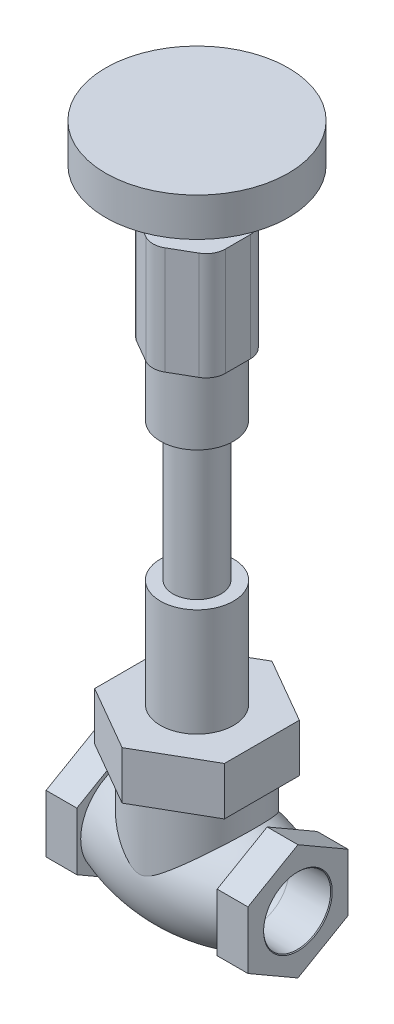
SolidWorks part; units mm, degrees
ref_plane "Front" through (0, 0, 0) normal (0, 0, 1) x (1, 0, 0)
ref_plane "Top" through (0, 0, 0) normal (0, 1, 0) x (1, 0, 0)
ref_plane "Right" through (0, 0, 0) normal (1, 0, 0) x (0, 0, -1)
sketch "Sketch1" plane through (0, 0, 0) normal (0, 0, 1) x (1, 0, 0)
  line L0 (-33.3375, 0) -> (33.3375, 0) construction
  line L1 (-33.3375, -11.0901) -> (-33.3375, 11.0901) construction
  line L2 (-33.3375, 11.0901) -> (-19.7815, 10.668)
  line L3 (-19.7815, 10.668) -> (19.7815, 10.668)
  line L4 (19.7815, 10.668) -> (33.3375, 11.0901)
  line L5 (33.3375, 11.0901) -> (33.3375, 16.51)
  line L6 (33.3375, 16.51) -> (23.1775, 16.51)
  line L7 (-33.3375, 11.0901) -> (-33.3375, 16.51)
  line L8 (-33.3375, 16.51) -> (-23.1775, 16.51)
  line L9 (-19.7815, 10.668) -> (-33.3375, 10.668) construction
  line L10 (33.3375, 11.0901) -> (33.3375, -11.0901) construction
  line L11 (0, 0) -> (0, 10.668) construction
  line L12 (0, 10.668) -> (0, 19.3675) construction
  line L13 (0, 0) -> (0, -10.668) construction
  line L14 (0, -10.668) -> (0, -19.3675) construction
  line L15 (-23.1775, 16.51) -> (-23.1775, 15.24)
  line L16 (23.1775, 16.51) -> (23.1775, 15.24)
  arc A0 (23.1775, 15.24) -> (-23.1775, 15.24) centre (0, -47.7715) ccw
  dimension "D1" = 66.675
  dimension "D2" = 1.783
  dimension "D3" = 13.556
  dimension "D4" = 21.336
  dimension "D5" = 33.02
  dimension "D7" = 38.735
  dimension "D6" = 10.16
  dimension "D8" = 1.27
revolve "Revolve1" add sketch "Sketch1" angle 360 about L0
sketch "Sketch2" plane through (0, 0, 0) normal (0, 0, 1) x (1, 0, 0)
  line L0 (0, 0) -> (0, 168.91)
  line L1 (7.9375, 78.105) -> (12.065, 78.105)
  line L2 (12.065, 78.105) -> (12.065, 42.545)
  line L3 (12.065, 42.545) -> (21.4312, 42.545)
  line L4 (21.4312, 42.545) -> (21.4312, 26.67)
  line L5 (21.4312, 26.67) -> (19.05, 26.67)
  line L6 (19.05, 26.67) -> (19.05, 0)
  line L7 (19.05, 0) -> (0, 0)
  line L8 (0, 0) -> (0, -19.3675) construction
  line L9 (7.9375, 78.105) -> (7.9375, 123.825)
  line L10 (7.9375, 123.825) -> (12.065, 123.825)
  line L11 (12.065, 123.825) -> (12.065, 146.05)
  line L12 (12.065, 146.05) -> (13.4937, 146.05)
  line L13 (13.4937, 146.05) -> (13.4937, 181.61)
  line L14 (13.4937, 181.61) -> (4.2545, 181.61)
  line L15 (4.2545, 181.61) -> (4.2545, 168.91)
  line L16 (4.2545, 168.91) -> (0, 168.91)
  line L17 (0, 168.91) -> (-4.2545, 168.91) construction
  arc A0 (-23.1775, -15.24) -> (23.1775, -15.24) centre (0, 47.7715) ccw construction
  dimension "D1" = 38.1
  dimension "D2" = 42.8625
  dimension "D3" = 15.875
  dimension "D4" = 61.9125
  dimension "D5" = 24.13
  dimension "D6" = 35.56
  dimension "D7" = 15.875
  dimension "D8" = 123.825
  dimension "D9" = 22.225
  dimension "D10" = 26.9875
  dimension "D11" = 35.56
  dimension "D12" = 8.509
  dimension "D13" = 12.7
revolve "Revolve2" add sketch "Sketch2" angle 360 about L8
sketch "Sketch3" plane through (0, 0, 0) normal (1, 0, 0) x (0, 0, -1)
  circle A0 centre (0, 0) radius 10.668 construction
  circle A1 centre (0, 0) radius 10.668
extrude "Cut-Extrude1" cut sketch "Sketch3" against normal through all and the other way through all
sketch "Sketch4" plane through (-33.3375, 0, 0) normal (-1, 0, 0) x (0, 0, 1)
  line L1 (0, 19.0641) -> (-16.51, 9.5321)
  line L2 (-16.51, 9.5321) -> (-16.51, -9.5321)
  line L3 (-16.51, -9.5321) -> (0, -19.0641)
  line L4 (0, -19.0641) -> (16.51, -9.5321)
  line L5 (16.51, -9.5321) -> (16.51, 9.5321)
  line L6 (16.51, 9.5321) -> (0, 19.0641)
  circle A0 centre (0, 0) radius 16.51 construction
  circle A2 centre (0, 0) radius 11.0901 construction
  circle A3 centre (0, 0) radius 11.0901
  circle A4 centre (0, 0) radius 16.51 construction
extrude "Boss-Extrude1" add sketch "Sketch4" against normal blind 10.16
ref_plane "Plane1" through (-19.7815, 0, 0) normal (1, 0, 0) x (0, 0, -1)
sketch "Sketch5" plane through (-19.7815, 0, 0) normal (1, 0, 0) x (0, 0, -1)
  circle A0 centre (0, 0) radius 10.668 construction
  circle A1 centre (0, 0) radius 10.668
curve "Helix/Spiral1"
sketch "Sketch6" plane through (0, 0, 0) normal (0, 0, 1) x (1, 0, 0)
  line L0 (-19.7815, 10.668) -> (-19.1012, 9.4896)
  line L1 (-19.7815, 10.668) -> (-19.7815, -10.668) construction
  line L2 (-19.1012, 9.4896) -> (-18.8744, 9.4896)
  line L3 (-18.8744, 9.4896) -> (-18.194, 10.668)
  line L4 (-18.194, 10.668) -> (-19.7815, 10.668)
  line L5 (-19.4413, 10.0788) -> (-18.5342, 10.0788) construction
  line L6 (-18.9878, 10.0788) -> (-18.9878, 9.4896) construction
  dimension "D1" = 60
  dimension "D2" = 0.2268
  dimension "D3" = 0.9071
sketch "Sketch7" plane through (-33.3375, 0, 0) normal (-1, 0, 0) x (0, 0, 1)
  circle A0 centre (0, 0) radius 11.3441
  circle A1 centre (0, 0) radius 11.0901 construction
  dimension "D1" = 0.254
sweep "Sweep1" [suppressed] add profiles "Sketch6" path "Helix/Spiral1"
extrude "Cut-Extrude2" [suppressed] cut sketch "Sketch7" along normal through all
extrude "Cut-Extrude3" cut sketch "Sketch7<2>" against normal through all draft 45
sketch "Sketch7<2>" plane through (-33.3375, 0, 0) normal (-1, 0, 0) x (0, 0, 1) same geometry as "Sketch7"
mirror "Mirror1" about plane through (0, 0, 0) normal (1, 0, 0) of "Cut-Extrude3", "Cut-Extrude2", "Sweep1", "Boss-Extrude1"
sketch "Sketch8" plane through (0, 42.545, 0) normal (0, 1, 0) x (1, 0, 0)
  line L1 (0, -24.7467) -> (21.4313, -12.3733)
  line L2 (21.4313, -12.3733) -> (21.4312, 12.3733)
  line L3 (21.4312, 12.3733) -> (0, 24.7467)
  line L4 (0, 24.7467) -> (-21.4312, 12.3733)
  line L5 (-21.4312, 12.3733) -> (-21.4313, -12.3733)
  line L6 (-21.4313, -12.3733) -> (0, -24.7467)
  circle A1 centre (0, 0) radius 21.4312 construction
  circle A2 centre (0, 0) radius 21.4312 construction
extrude "Boss-Extrude2" add sketch "Sketch8" against normal up to surface (15.875 mm away) up to face at (0, 26.67, 21.4312)
sketch "Sketch9" plane through (0, 181.61, -183.515) normal (0, -1, 0) x (1, 0, 0)
  line L1 (-3.175, 197.2632) -> (-10.3187, 193.1387)
  line L2 (-13.4937, 187.6394) -> (-13.4937, 179.3906)
  line L3 (-10.3187, 173.8913) -> (-3.175, 169.7668)
  line L4 (3.175, 169.7668) -> (10.3187, 173.8913)
  line L6 (13.4937, 179.3906) -> (13.4937, 187.6394)
  line L7 (10.3187, 193.1387) -> (3.175, 197.2632)
  circle A0 centre (0, 183.515) radius 13.4937 construction
  circle A1 centre (0, 183.515) radius 13.4937 construction
  arc A2 (10.3187, 173.8913) -> (13.4937, 179.3906) centre (7.1437, 179.3906) ccw
  arc A3 (-3.175, 169.7668) -> (3.175, 169.7668) centre (0, 175.2661) ccw
  arc A4 (-13.4937, 179.3906) -> (-10.3187, 173.8913) centre (-7.1437, 179.3906) ccw
  arc A5 (-10.3187, 193.1387) -> (-13.4937, 187.6394) centre (-7.1437, 187.6394) ccw
  arc A6 (-3.175, 197.2632) -> (3.175, 197.2632) centre (0, 191.7639) cw
  arc A7 (13.4937, 187.6394) -> (10.3187, 193.1387) centre (7.1437, 187.6394) ccw
  circle A8 centre (0, 183.515) radius 4.2545 construction
  circle A9 centre (0, 183.515) radius 4.2545
  dimension "D1" = 6.35
extrude "Boss-Extrude4" add sketch "Sketch9" along normal up to surface (35.56 mm away) up to face at (0, 146.05, 13.4937)
sketch "Sketch11" plane through (0, 0, 0) normal (0, 0, 1) x (1, 0, 0)
  line L0 (0, 168.91) -> (0, 209.55)
  line L2 (0, 209.55) -> (-30.1625, 209.55)
  line L3 (-30.1625, 209.55) -> (-30.1625, 196.85)
  line L4 (-30.1625, 196.85) -> (-7.9375, 196.85)
  line L5 (-7.9375, 196.85) -> (-7.9375, 190.5)
  line L6 (-7.9375, 190.5) -> (-4.2545, 190.5)
  line L7 (-4.2545, 190.5) -> (-4.2545, 168.91)
  line L8 (4.2545, 168.91) -> (-4.2545, 168.91) construction
  line L9 (-4.2545, 168.91) -> (0, 168.91)
  line L11 (0, 168.91) -> (0, 0) construction
  dimension "D1" = 209.55
  dimension "D2" = 60.325
  dimension "D3" = 12.7
  dimension "D4" = 19.05
  dimension "D5" = 15.875
revolve "Revolve4" add sketch "Sketch11" angle 360 about L11
equation "\"D1@Boss-Extrude1\" = \"D6@Sketch1\""
